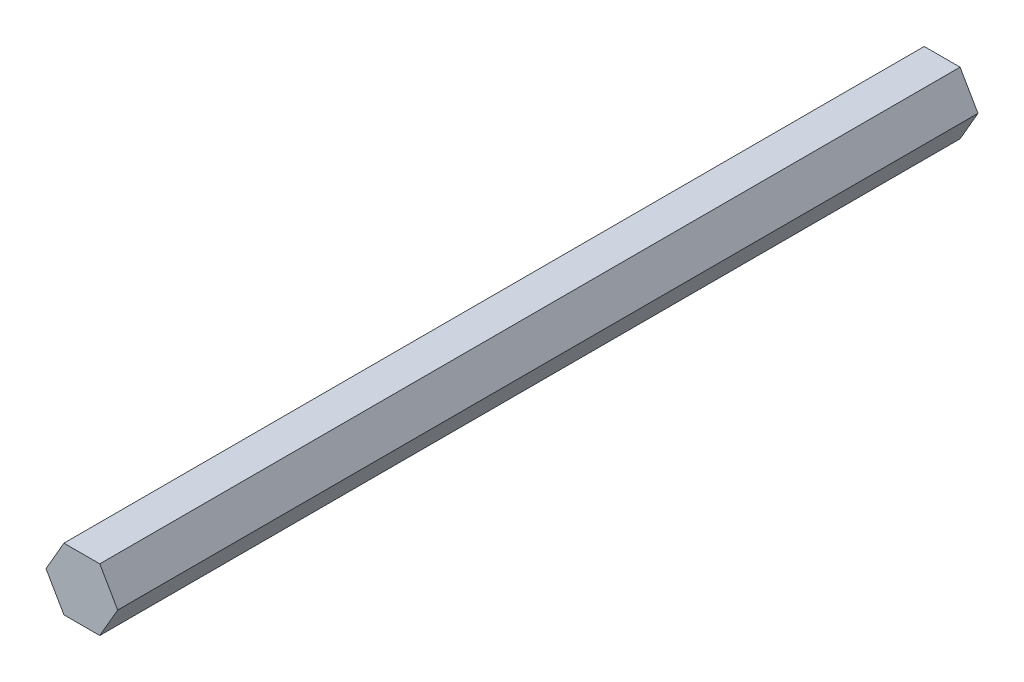
SolidWorks part; units mm, degrees
material "AISI 1020 Steel, Cold Rolled"
ref_plane "Front Plane" through (0, 0, 0) normal (0, 0, 1) x (1, 0, 0)
ref_plane "Top Plane" through (0, 0, 0) normal (0, 1, 0) x (1, 0, 0)
ref_plane "Right Plane" through (0, 0, 0) normal (1, 0, 0) x (0, 0, -1)
other "Configuration Table"
sketch "Sketch1" plane through (0, 0, 0) normal (0, 0, 1) x (1, 0, 0)
  line L1 (6.35, 0) -> (3.175, 5.4993)
  line L2 (3.175, 5.4993) -> (-3.175, 5.4993)
  line L3 (-3.175, 5.4993) -> (-6.35, 0)
  line L4 (-6.35, 0) -> (-3.175, -5.4993)
  line L5 (-3.175, -5.4993) -> (3.175, -5.4993)
  line L6 (3.175, -5.4993) -> (6.35, 0)
  circle A0 centre (0, 0) radius 5.4993 construction
  dimension "D1" = 12.7
extrude "Boss-Extrude1" add sketch "Sketch1" along normal mid plane 152.4
equation "\"length\"= 6"
equation "\"D1@Boss-Extrude1\"=\"length\""
